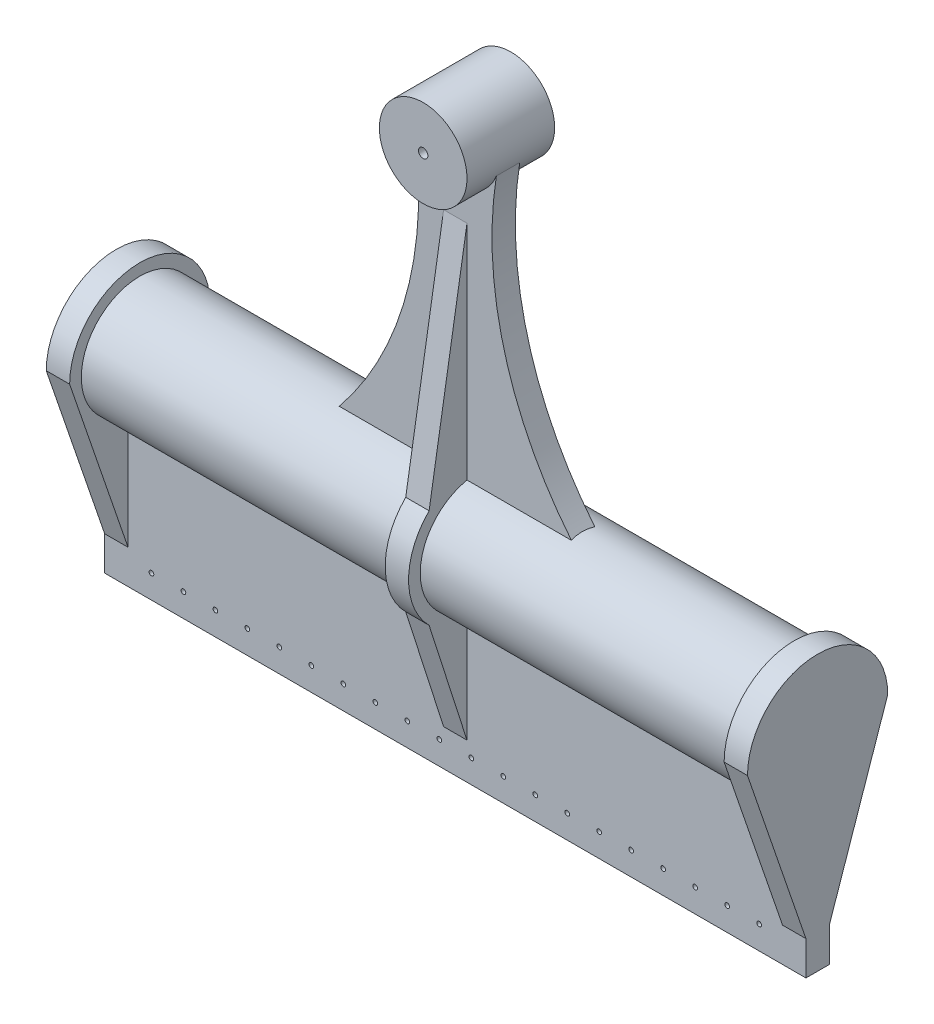
SolidWorks part; units mm, degrees
ref_plane "Front Plane" through (0, 0, 0) normal (1, 0, 0) x (0, 1, 0)
ref_plane "Top Plane" through (0, 0, 0) normal (0, 0, 1) x (0, 1, 0)
ref_plane "Right Plane" through (0, 0, 0) normal (0, 1, 0) x (-1, 0, 0)
sketch "Sketch1" plane through (0, 0, 0) normal (0, 0, 1) x (0, 1, 0)
  line L1 (-44.45, -76.2) -> (0, -76.2)
  line L2 (-44.45, -76.2) -> (-44.45, 76.2)
  line L3 (-44.45, 76.2) -> (0, 76.2)
  line L4 (0, -76.2) -> (0, 76.2)
  line L5 (-44.45, -76.2) -> (0, 76.2) construction
  line L6 (-44.45, 76.2) -> (0, -76.2) construction
  circle A0 centre (-39.37, -66.04) radius 0.508
  circle A1 centre (-39.37, -59.0884) radius 0.508
  circle A2 centre (-39.37, -52.1368) radius 0.508
  circle A3 centre (-39.37, -45.1853) radius 0.508
  circle A4 centre (-39.37, -38.2337) radius 0.508
  circle A5 centre (-39.37, -31.2821) radius 0.508
  circle A6 centre (-39.37, -24.3305) radius 0.508
  circle A7 centre (-39.37, -17.3789) radius 0.508
  circle A8 centre (-39.37, -10.4274) radius 0.508
  circle A9 centre (-39.37, -3.4758) radius 0.508
  circle A10 centre (-39.37, 3.4758) radius 0.508
  circle A11 centre (-39.37, 10.4274) radius 0.508
  circle A12 centre (-39.37, 17.3789) radius 0.508
  circle A13 centre (-39.37, 24.3305) radius 0.508
  circle A14 centre (-39.37, 31.2821) radius 0.508
  circle A15 centre (-39.37, 38.2337) radius 0.508
  circle A16 centre (-39.37, 45.1853) radius 0.508
  circle A17 centre (-39.37, 52.1368) radius 0.508
  circle A18 centre (-39.37, 59.0884) radius 0.508
  circle A19 centre (-39.37, 66.04) radius 0.508
extrude "Boss-Extrude1" add sketch "Sketch1" along normal blind 2.54 and the other way blind 2.54
sketch "Sketch2" plane through (0, 0, 0) normal (1, 0, 0) x (0, 1, 0)
  circle A0 centre (0, 0) radius 12.7
extrude "Boss-Extrude2" add sketch "Sketch2" along normal blind 76.2 and the other way blind 76.2
sketch "Sketch3" plane through (0, 0, 0) normal (1, 0, 0) x (0, 1, 0)
  line L0 (0, 15.24) -> (-44.45, 0)
  line L1 (-44.45, 0) -> (0, -15.24)
  arc A0 (0, -15.24) -> (0, 15.24) centre (0, 0) ccw
extrude "Boss-Extrude3" add sketch "Sketch3" along normal blind 5.08 from offset 71.12
sketch "Sketch4" plane through (0, 0, 0) normal (1, 0, 0) x (0, 1, 0)
  line L0 (0, 15.24) -> (-44.45, 0)
  line L1 (-44.45, 0) -> (0, -15.24)
  arc A0 (0, -15.24) -> (0, 15.24) centre (0, 0) ccw
extrude "Boss-Extrude4" add sketch "Sketch4" against normal blind 5.08 from offset 71.12 offset against normal yes
sketch "Sketch5" plane through (0, 0, 0) normal (0, 0, 1) x (0, 1, 0)
  line L0 (0, -38.1) -> (0, 38.1)
  line L1 (76.2, 9.525) -> (76.2, -9.525)
  arc A0 (0, 38.1) -> (76.2, 9.525) centre (60.8501, 84.4794) ccw
  arc A1 (76.2, -9.525) -> (0, -38.1) centre (60.8501, -84.4794) ccw
extrude "Boss-Extrude5" add sketch "Sketch5" along normal blind 2.54 and the other way blind 2.54
sketch "Sketch6" plane through (0, 0, 0) normal (0, 0, 1) x (0, 1, 0)
  circle A0 centre (76.2, 0) radius 9.525
  circle A1 centre (76.2, 0) radius 1.016
extrude "Boss-Extrude6" add sketch "Sketch6" along normal blind 9.525 and the other way blind 9.525
sketch "Sketch7" plane through (0, 0, 0) normal (1, 0, 0) x (0, 1, 0)
  line L0 (-44.45, 0) -> (-10.7763, 10.7763)
  line L1 (10.7763, 10.7763) -> (76.2, 0)
  line L2 (76.2, 0) -> (10.7763, -10.7763)
  line L3 (-10.7763, -10.7763) -> (-44.45, 0)
  arc A0 (-10.7763, 10.7763) -> (10.7763, 10.7763) centre (0, 0) cw
  arc A1 (10.7763, -10.7763) -> (-10.7763, -10.7763) centre (0, 0) cw
extrude "Boss-Extrude7" add sketch "Sketch7" along normal blind 2.54 and the other way blind 2.54
